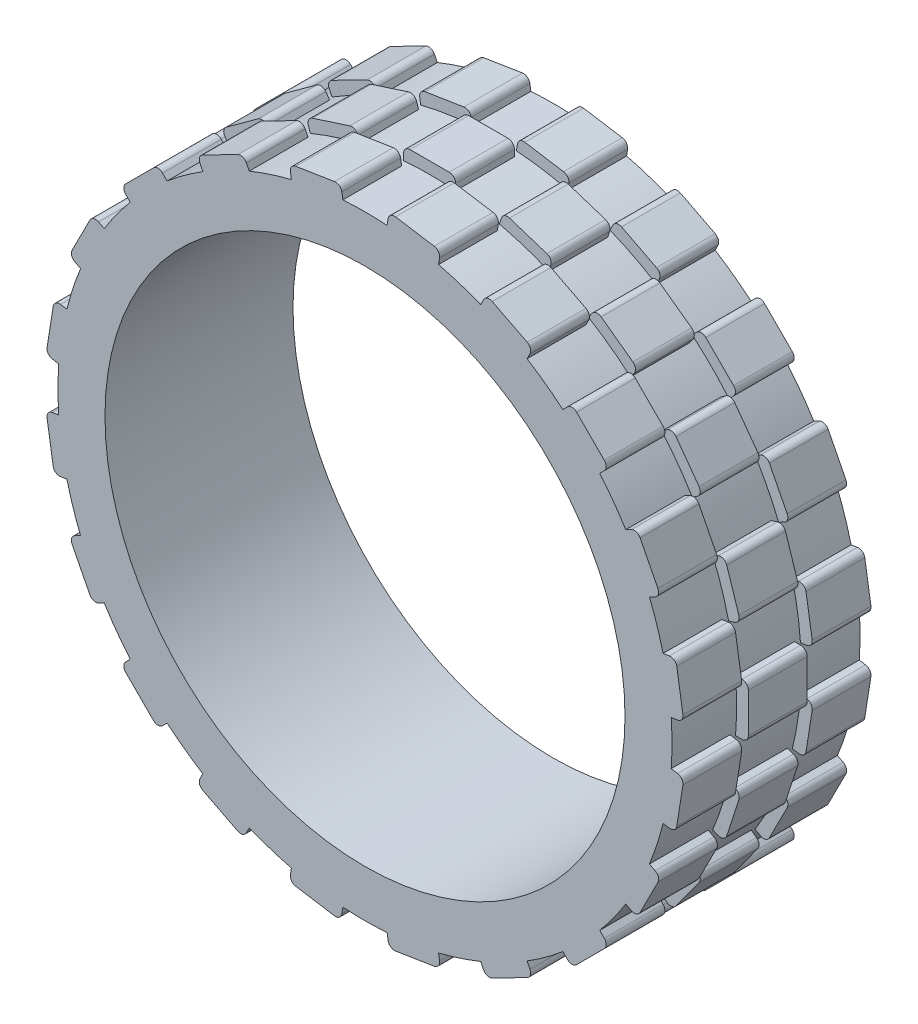
SolidWorks part; units mm, degrees
ref_plane "Front Plane" through (0, 0, 0) normal (0, 0, 1) x (1, 0, 0)
ref_plane "Top Plane" through (0, 0, 0) normal (0, 1, 0) x (1, 0, 0)
ref_plane "Right Plane" through (0, 0, 0) normal (1, 0, 0) x (0, 0, -1)
sketch "Sketch1" plane through (0, 0, 0) normal (0, 0, 1) x (1, 0, 0)
  circle A0 centre (0, 0) radius 22.125
  circle A1 centre (0, 0) radius 26.125
  dimension "D1" = 4
  dimension "D2" = 44.25
extrude "Boss-Extrude1" add sketch "Sketch1" along normal blind 16
ref_plane "Plane1" through (0, 0, 8) normal (0, 0, -1) x (-1, 0, 0)
sketch "Sketch4" plane through (0, 0, 8) normal (0, 0, -1) x (-1, 0, 0)
  line L0 (0, 0) -> (0, 10.3702) construction
  line L1 (-1.6693, 27.125) -> (1.6693, 27.125)
  line L2 (-2.216, 26.5782) -> (-2.216, 24.0721)
  line L3 (-2.216, 24.0721) -> (2.216, 24.0721)
  line L4 (2.216, 26.5782) -> (2.216, 24.0721)
  line L5 (-2.216, 27.125) -> (-2.216, 26.5782) construction
  line L6 (-2.216, 27.125) -> (-1.6693, 27.125) construction
  line L7 (1.6693, 27.125) -> (2.216, 27.125) construction
  line L8 (2.216, 27.125) -> (2.216, 26.5782) construction
  line L9 (-12.8814, 26.125) -> (-4.676, 26.125) construction
  arc A0 (-2.216, 26.5782) -> (-1.6693, 27.125) centre (-1.6693, 26.5782) cw
  arc A1 (2.216, 26.5782) -> (1.6693, 27.125) centre (1.6693, 26.5782) ccw
  circle A3 centre (0, 0) radius 26.125 construction
  point P19 (0, 0)
  dimension "D1" = 1
extrude "Boss-Extrude2" add sketch "Sketch4" along normal blind 2.5 and the other way blind 2.5
ref_axis "Axis1" through (0, 0, 17.0902) along (0, 0, -1)
pattern_circular "CirPattern1" count 20 over 360 about axis through (0, 0, 17.0902) along (0, 0, -1) of "Boss-Extrude2"
ref_plane "Plane3" through (0, 0, 3) normal (0, 0, -1) x (-1, 0, 0)
sketch "Sketch6" plane through (0, 0, 3) normal (0, 0, 1) x (1, 0, 0)
  line L0 (0, 0) -> (1.505, 9.5019) construction
  line L1 (2.5946, 27.0522) -> (5.892, 26.5299)
  line L2 (1.969, 26.5977) -> (1.5853, 24.1746)
  line L3 (1.5853, 24.1746) -> (5.9627, 23.4813)
  line L4 (6.3465, 25.9044) -> (5.9627, 23.4813)
  line L5 (2.0546, 27.1377) -> (1.969, 26.5977) construction
  line L6 (2.0546, 27.1377) -> (2.5946, 27.0522) construction
  line L7 (5.892, 26.5299) -> (6.432, 26.4444) construction
  line L8 (6.432, 26.4444) -> (6.3465, 25.9044) construction
  line L9 (-17.3497, 29.1986) -> (-9.8315, 28.0078) construction
  line L10 (0, 48.4782) -> (0, 9.2186) construction
  arc A0 (1.969, 26.5977) -> (2.5946, 27.0522) centre (2.5091, 26.5122) cw
  arc A1 (6.3465, 25.9044) -> (5.892, 26.5299) centre (5.8065, 25.9899) ccw
  circle A2 centre (0, 0) radius 26.125 construction
  dimension "D1" = 1
  dimension "D3" = 0.5468
  dimension "D2" = 4.432
  dimension "D4" = 2
  dimension "D5" = 9
extrude "Boss-Extrude3" add sketch "Sketch6" along normal blind 2 and the other way blind 3
pattern_circular "CirPattern2" count 20 over 360 about axis through (0, 0, 17.0902) along (0, 0, -1) of "Boss-Extrude3"
mirror "Mirror1" about plane through (0, 0, 8) normal (0, 0, -1) of "CirPattern2"
